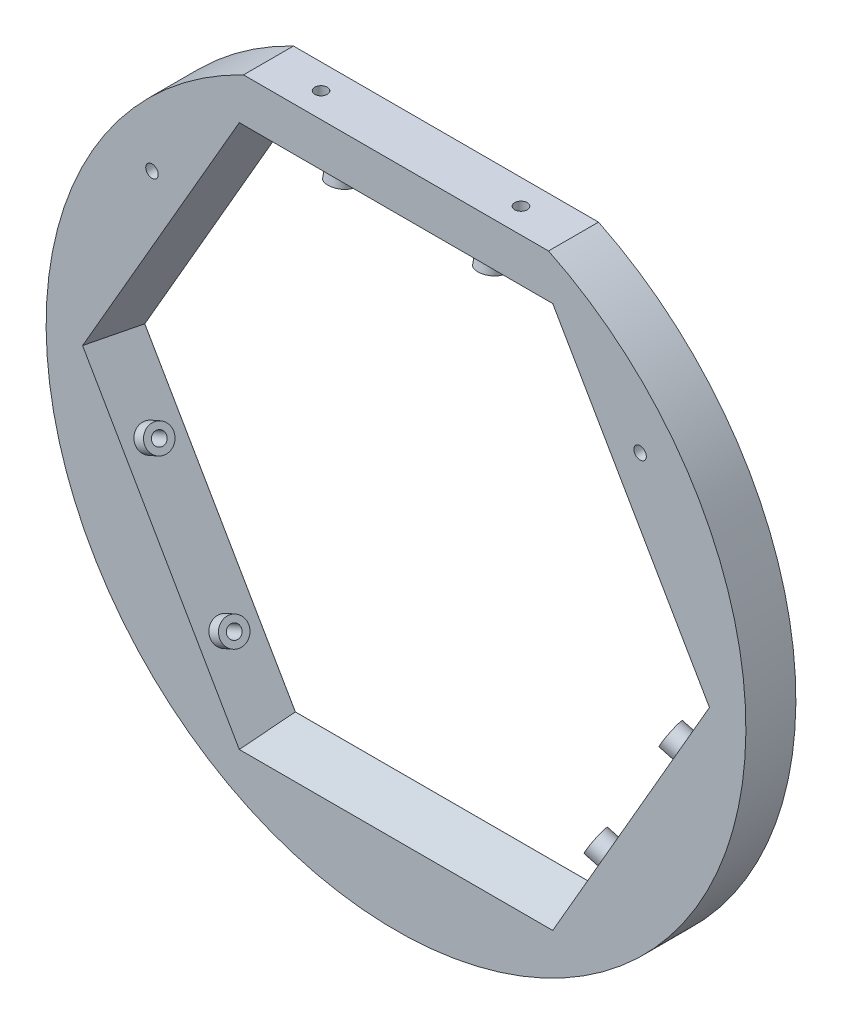
SolidWorks part; units mm, degrees
ref_plane "Plan de face" through (0, 0, 0) normal (0, 0, 1) x (1, 0, 0)
ref_plane "Plan de dessus" through (0, 0, 0) normal (0, 1, 0) x (1, 0, 0)
ref_plane "Plan de droite" through (0, 0, 0) normal (1, 0, 0) x (0, 0, -1)
sketch "Esquisse1" plane through (0, 0, 0) normal (0, 0, 1) x (1, 0, 0)
  line L1 (60.258, 0) -> (30.129, 52.185)
  line L2 (30.129, 52.185) -> (-30.129, 52.185)
  line L3 (-30.129, 52.185) -> (-60.258, 0)
  line L4 (-60.258, 0) -> (-30.129, -52.185)
  line L5 (-30.129, -52.185) -> (30.129, -52.185)
  line L6 (30.129, -52.185) -> (60.258, 0)
  circle A0 centre (0, 0) radius 70
  circle A1 centre (0, 0) radius 52.185 construction
  dimension "D1" = 140
  dimension "D2" = 104.37
extrude "Boss.-Extru.1" add sketch "Esquisse1" along normal blind 10
chamfer "Chanfrein1" distance 2.12 angle 78 6 edges at (-45.1935, 26.0925, 10) (-45.1935, -26.0925, 10) (0, -52.185, 10) (45.1935, -26.0925, 10) (45.1935, 26.0925, 10) (0, 52.185, 10) first distance on face at (70, 0, 10)
sketch "Esquisse2" plane through (-43.2353, -24.9619, -10.6116) normal (0.8471, 0.4891, 0.2079) x (0.1801, 0.104, -0.9781)
  line L0 (-10.8487, 0) -> (-21.0721, 0) construction
  line L1 (-10.8487, 30.1258) -> (-10.8487, -30.1258) construction
  line L2 (-21.0721, -31.353) -> (-21.0721, 31.353) construction
  line L3 (-16.5404, 15) -> (-16.5404, -15) construction
  circle A0 centre (-16.5404, 15) radius 1.25
  circle A1 centre (-16.5404, -15) radius 1.25
  point P12 (-16.5404, 0)
  point P13 (-15.9604, 0)
  dimension "D1" = 2.5
  dimension "D2" = 0.58
  dimension "D3" = 15
extrude "Enlèv. mat.-Extru.1" cut sketch "Esquisse2" against normal blind 8
sketch "Esquisse3" plane through (-43.2353, -24.9619, -10.6116) normal (0.8471, 0.4891, 0.2079) x (0.1801, 0.104, -0.9781)
  circle A0 centre (-16.5404, -15) radius 2.5
  circle A1 centre (-16.5404, 15) radius 2.5
  circle A2 centre (-16.5404, -15) radius 1.25 construction
  circle A3 centre (-16.5404, 15) radius 1.25 construction
  circle A4 centre (-16.5404, -15) radius 1.25
  circle A5 centre (-16.5404, 15) radius 1.25
  dimension "D1" = 5
extrude "Boss.-Extru.2" add sketch "Esquisse3" along normal blind 3
pattern_circular "Répétition circulaire1" count 3 over 360 about axis through (0, 0, 0) along (0, 0, 1) of "Enlèv. mat.-Extru.1", "Boss.-Extru.2"
sketch "Esquisse4" plane through (0, 0, 0) normal (0, 0, -1) x (-1, 0, 0)
  line L0 (30.5123, 63) -> (-30.5123, 63)
  circle A0 centre (0, 0) radius 70 construction
  arc A1 (30.5123, 63) -> (-30.5123, 63) centre (0, 0) ccw
  dimension "D1" = 61.0246
extrude "Enlèv. mat.-Extru.2" cut sketch "Esquisse4" against normal up to next
sketch "Esquisse5" plane through (0, 63, 0) normal (0, 1, 0) x (1, 0, 0)
  line L0 (-30.5123, -10) -> (-30.5123, 0) construction
  line L1 (-20, -5) -> (20, -5) construction
  line L4 (30.5123, -10) -> (-30.5123, -10) construction
  circle A0 centre (-20, -5) radius 1.25
  circle A1 centre (20, -5) radius 1.25
  point P4 (0, -5)
  point P9 (-30.5123, -5)
  point P10 (0, -10)
  dimension "D1" = 2.5
  dimension "D2" = 40
extrude "Enlèv. mat.-Extru.3" cut sketch "Esquisse5" against normal blind 8
sketch "Esquisse6" plane through (0, 0, 0) normal (0, 0, -1) x (-1, 0, 0)
  line L0 (48.824, 37.1794) -> (-48.824, 37.1794) construction
  line L1 (-30.1258, 52.1794) -> (30.1258, 52.1794) construction
  line L2 (56.3524, 41.526) -> (41.2955, 32.8329) construction
  line L3 (30.1258, 52.1794) -> (60.2516, 0) construction
  line L4 (-41.2955, 32.8329) -> (-56.3524, 41.526) construction
  line L5 (-60.2516, 0) -> (-30.1258, 52.1794) construction
  circle A0 centre (48.824, 37.1794) radius 1.25
  circle A1 centre (-48.824, 37.1794) radius 1.25
  arc A2 (-30.5123, 63) -> (30.5123, 63) centre (0, 0) ccw construction
  point P18 (-48.824, 37.1794)
  point P19 (48.824, 37.1794)
  dimension "D2" = 2.5
  dimension "D1" = 15
extrude "Enlèv. mat.-Extru.4" cut sketch "Esquisse6" against normal up to next
